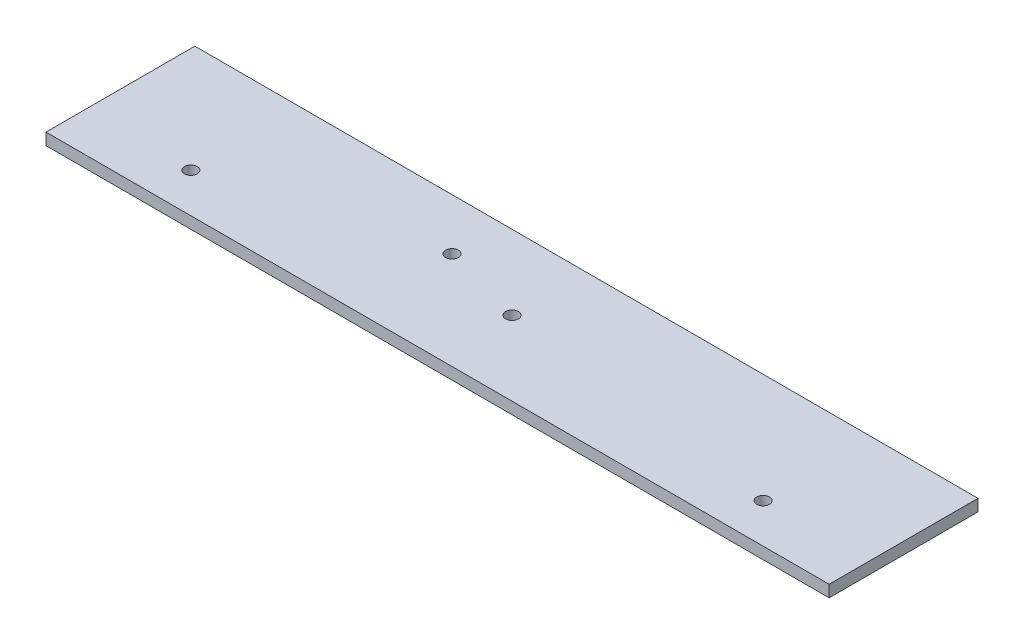
SolidWorks part; units mm, degrees
ref_plane "Front Plane" through (0, 0, 0) normal (0, 0, 1) x (1, 0, 0)
ref_plane "Top Plane" through (0, 0, 0) normal (0, 1, 0) x (1, 0, 0)
ref_plane "Right Plane" through (0, 0, 0) normal (1, 0, 0) x (0, 0, -1)
sketch "Sketch1" plane through (0, 0, 0) normal (0, 1, 0) x (1, 0, 0)
  line L0 (-71, -8.695) -> (71, -8.695) construction
  line L1 (0, 0) -> (0, 5.75) construction
  line L2 (-97.1504, -18.4656) -> (97.1504, -18.4656)
  line L3 (-97.1504, -18.4656) -> (-97.1504, 18.4656)
  line L4 (-97.1504, 18.4656) -> (97.1504, 18.4656)
  line L5 (97.1504, -18.4656) -> (97.1504, 18.4656)
  line L6 (-97.1504, -18.4656) -> (97.1504, 18.4656) construction
  line L7 (-97.1504, 18.4656) -> (97.1504, -18.4656) construction
  line L8 (0, 5.75) -> (-20.62, 5.75) construction
  circle A0 centre (-71, -8.695) radius 1.5875
  circle A1 centre (71, -8.695) radius 1.5875
  circle A2 centre (0, 0) radius 1.5875
  circle A3 centre (-20.62, 5.75) radius 1.5875
  point P6 (0, 0)
  dimension "D2" = 3.175
  dimension "D1" = 142
  dimension "D3" = 5.75
  dimension "D4" = 20.62
  dimension "D5" = 8.695
extrude "Boss-Extrude1" add sketch "Sketch1" along normal mid plane 2.921
sketch "Sketch2" plane through (0, -1.4605, 0) normal (0, -1, 0) x (-1, 0, 0)
  line L0 (20.62, 5.75) -> (13.8061, 5.75) construction
